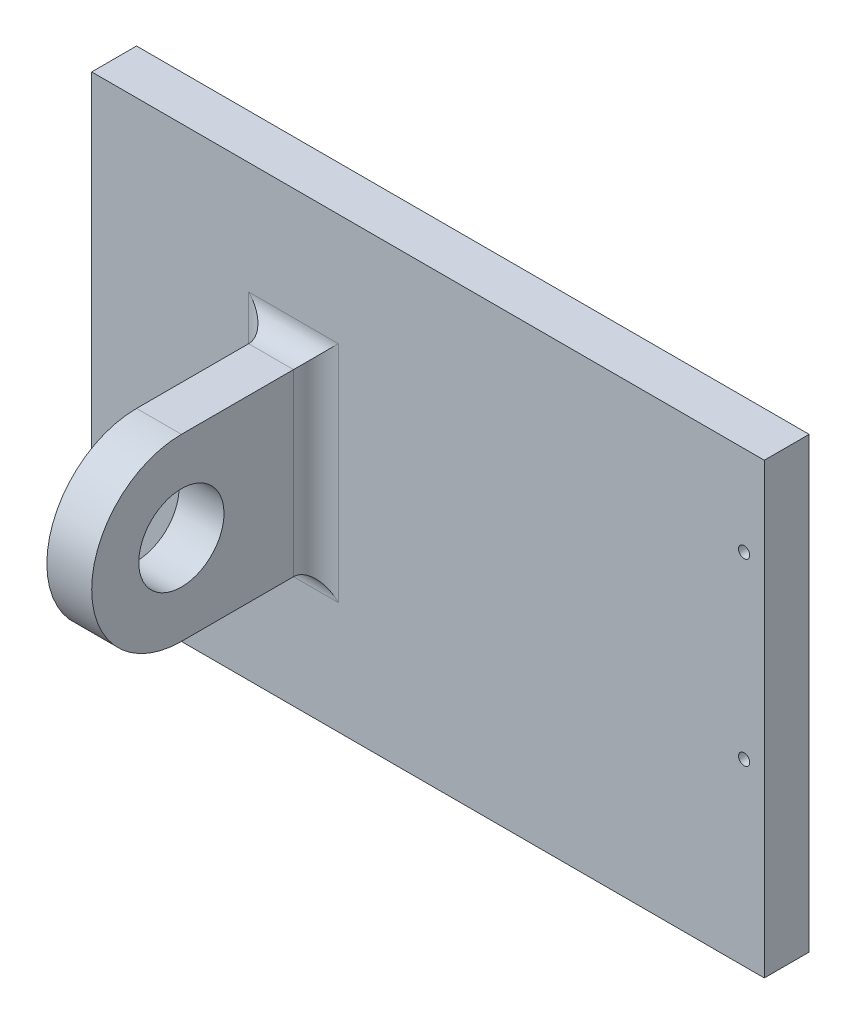
SolidWorks part; units mm, degrees
ref_plane "正面" through (0, 0, 0) normal (0, 0, 1) x (1, 0, 0)
ref_plane "平面" through (0, 0, 0) normal (0, 1, 0) x (1, 0, 0)
ref_plane "右側面" through (0, 0, 0) normal (1, 0, 0) x (0, 0, -1)
sketch "ｽｹｯﾁ2" plane through (0, 0, 0) normal (0, 0, 1) x (1, 0, 0)
  line L1 (-75, 50) -> (75, 50)
  line L2 (-75, 50) -> (-75, -50)
  line L3 (-75, -50) -> (75, -50)
  line L4 (75, 50) -> (75, -50)
  line L5 (-75, 50) -> (75, -50) construction
  line L6 (-75, -50) -> (75, 50) construction
  point P0 (0, 0)
  dimension "D1" = 150
  dimension "D2" = 100
extrude "ﾎﾞｽ - 押し出し1" add sketch "ｽｹｯﾁ2" along normal blind 10
sketch "ｽｹｯﾁ3" plane through (0, 0, 0) normal (0, 0, 1) x (1, 0, 0)
  line L0 (-35, 20) -> (-35, -20)
  line L1 (-35, -20) -> (-25, -20)
  line L2 (-25, -20) -> (-25, 20)
  line L3 (-25, 20) -> (-35, 20)
  dimension "D1" = 10
  dimension "D2" = 20
  dimension "D3" = 20
  dimension "D4" = 25
extrude "ﾎﾞｽ - 押し出し2" add sketch "ｽｹｯﾁ3" along normal blind 40
ref_plane "平面1" through (-35, 0, 0) normal (-1, 0, 0) x (0, 0, 1)
sketch "ｽｹｯﾁ4" plane through (-35, 0, 0) normal (-1, 0, 0) x (0, 0, 1)
  line L0 (40, 20) -> (40, -20) construction
  circle A0 centre (40, 0) radius 20
extrude "ﾎﾞｽ - 押し出し3" add sketch "ｽｹｯﾁ4" against normal blind 10
sketch "ｽｹｯﾁ5" plane through (-35, 0, 0) normal (-1, 0, 0) x (0, 0, 1)
  circle A0 centre (40, 0) radius 9.5
  dimension "D1" = 19
extrude "ｶｯﾄ - 押し出し1" cut sketch "ｽｹｯﾁ5" against normal blind 10
hole_wizard "M3x0.5 ねじ穴2" positions "ｽｹｯﾁ10" profile "ｽｹｯﾁ11" tap size "M3x0.5" standard "JIS" end condition through all
sketch "ｽｹｯﾁ10" plane through (0, 0, 10) normal (0, 0, 1) x (1, 0, 0)
  point P0 (70.5, -10.0009)
  point P3 (70.5, 29.9991)
sketch "ｽｹｯﾁ11" plane through (70.5, -10.0009, 10) normal (1, 0, 0) x (0, -1, 0)
  line L0 (0, 0) -> (0, 10)
  line L1 (0, 10) -> (1.25, 10)
  line L2 (1.25, 10) -> (1.25, 0)
  line L5 (1.25, 0) -> (0, 0)
  line L11 (0, -6.35) -> (0, 107.95) construction
  dimension "次ｻｰﾌｪｽまでのねじ下穴ﾄﾞﾘﾙ直径" = 2.5
  dimension "次ｻｰﾌｪｽまでのねじ下穴ﾄﾞﾘﾙの深さ" = 10
cosmetic thread "穴のねじ山4" parameters "D2"=3
cosmetic thread "穴のねじ山5" parameters "D2"=3
fillet "ﾌｨﾚｯﾄ1" radius 5 4 edges at (-30, -20, 10) (-35, 0, 10) (-30, 20, 10) (-25, 0, 10)
